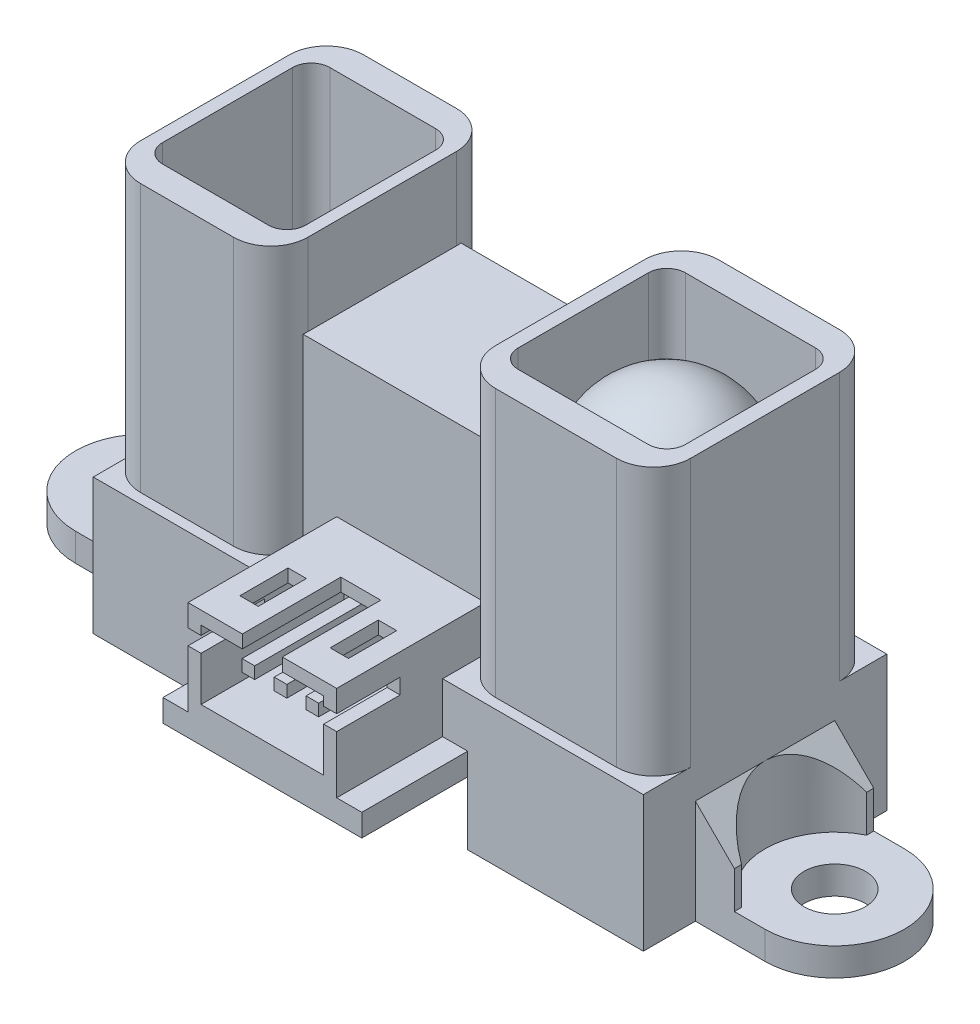
SolidWorks part; units mm, degrees
ref_plane "前视基准面" through (0, 0, 0) normal (0, 0, 1) x (1, 0, 0)
ref_plane "上视基准面" through (0, 0, 0) normal (0, 1, 0) x (1, 0, 0)
ref_plane "右视基准面" through (0, 0, 0) normal (1, 0, 0) x (0, 0, -1)
sketch "草图1" plane through (0, 0, 0) normal (0, 1, 0) x (1, 0, 0)
  line L0 (-14.8, 6.55) -> (14.8, -6.55) construction
  line L1 (-14.8, 6.55) -> (14.8, 6.55)
  line L2 (-14.8, 6.55) -> (-14.8, -6.55)
  line L3 (-14.8, -6.55) -> (14.8, -6.55)
  line L4 (14.8, 6.55) -> (14.8, -6.55)
  line L5 (14.8, 6.55) -> (-14.8, -6.55) construction
  dimension "D1" = 29.6
  dimension "D2" = 13.1
extrude "凸台-拉伸1" add sketch "草图1" along normal blind 7.3
sketch "草图2" plane through (0, 7.3, 0) normal (0, 1, 0) x (1, 0, 0)
  line L0 (14.8, -6.55) -> (14.8, 6.55) construction
  line L1 (4.3, 6) -> (14.8, 6)
  line L2 (4.3, 6) -> (4.3, -6)
  line L3 (4.3, -6) -> (14.8, -6)
  line L4 (14.8, 6) -> (14.8, -6)
  line L5 (-20.4467, 0) -> (27.7818, 0) construction
  line L6 (14.8, 6.55) -> (-14.8, 6.55) construction
  line L7 (-14.8, -6.55) -> (14.8, -6.55) construction
  line L8 (4.3, 6) -> (-21.835, 6) construction
  line L9 (4.3, -6) -> (-21.835, -6) construction
  line L10 (-14.8, 6.55) -> (-14.8, -6.55) construction
  line L11 (-14.8, 6) -> (-5.8, 6)
  line L12 (-14.8, 6) -> (-14.8, -6)
  line L13 (-14.8, -6) -> (-5.8, -6)
  line L14 (-5.8, 6) -> (-5.8, -6)
  dimension "D1" = 10.5
  dimension "D2" = 12
  dimension "D3" = 9
extrude "凸台-拉伸2" add sketch "草图2" along normal blind 14.4
sketch "草图3" plane through (0, 7.3, 0) normal (0, 1, 0) x (1, 0, 0)
  line L0 (-5.8, -6) -> (-5.8, 6) construction
  line L1 (-5.8, 4.25) -> (4.3, 4.25)
  line L2 (-5.8, 4.25) -> (-5.8, -4.25)
  line L3 (-5.8, -4.25) -> (4.3, -4.25)
  line L4 (4.3, 4.25) -> (4.3, -4.25)
  line L5 (4.3, 6) -> (4.3, -6) construction
  line L6 (-18.5434, 0) -> (19.3503, 0) construction
  dimension "D1" = 8.5
extrude "凸台-拉伸3" add sketch "草图3" along normal blind 10
fillet "圆角1" radius 2 8 edges at (14.8, 14.5, 6) (4.3, 14.5, 6) (14.8, 14.5, -6) (4.3, 14.5, -6) (-5.8, 14.5, -6) (-14.8, 14.5, -6) (-5.8, 14.5, 6) (-14.8, 14.5, 6)
sketch "草图4" plane through (0, 21.7, 0) normal (0, 1, 0) x (1, 0, 0)
  line L0 (-19.2678, 0) -> (22.6472, 0) construction
  line L2 (5.0163, -4.5) -> (14.0163, -4.5)
  line L3 (5.0163, -4.5) -> (5.0163, 4.5)
  line L4 (5.0163, 4.5) -> (14.0163, 4.5)
  line L5 (14.0163, -4.5) -> (14.0163, 4.5)
  line L6 (5.0163, -4.5) -> (14.0163, 4.5) construction
  line L7 (5.0163, 4.5) -> (14.0163, -4.5) construction
  line L8 (-14.1217, -4.5) -> (-6.4217, -4.5)
  line L9 (-14.1217, -4.5) -> (-14.1217, 4.5)
  line L10 (-14.1217, 4.5) -> (-6.4217, 4.5)
  line L11 (-6.4217, -4.5) -> (-6.4217, 4.5)
  line L12 (-14.1217, -4.5) -> (-6.4217, 4.5) construction
  line L13 (-14.1217, 4.5) -> (-6.4217, -4.5) construction
  point P3 (9.5163, 0)
  point P8 (-10.2717, 0)
  dimension "D1" = 9
  dimension "D2" = 9
  dimension "D3" = 9
  dimension "D4" = 7.7
extrude "切除-拉伸2" cut sketch "草图4" against normal blind 10
sketch "草图5" plane through (0, 0, 0) normal (0, -1, 0) x (1, 0, 0)
  line L0 (-22.468, 0) -> (25.1594, 0) construction
  line L1 (-18.55, 0) -> (18.55, 0) construction
  line L2 (-18.55, 3.75) -> (18.55, 3.75)
  line L3 (-18.55, -3.75) -> (18.55, -3.75)
  line L4 (0, 10.6195) -> (0, -15.0191) construction
  line L5 (-14.8, -6.55) -> (-14.8, 6.55) construction
  line L6 (14.8, 6.55) -> (14.8, -6.55) construction
  arc A0 (-18.55, 3.75) -> (-18.55, -3.75) centre (-18.55, 0) ccw
  arc A1 (18.55, -3.75) -> (18.55, 3.75) centre (18.55, 0) ccw
  circle A2 centre (-18.55, 0) radius 3.75 construction
  circle A3 centre (18.55, 0) radius 3.75 construction
  point P5 (0, 0)
  dimension "D2" = 7.5
extrude "凸台-拉伸4" add sketch "草图5" against normal blind 5.6
sketch "草图6" plane through (0, 0, -3.75) normal (0, 0, -1) x (-1, 0, 0)
  line L0 (0, 22.8299) -> (0, -7.404) construction
  line L1 (-14.8, 5.6) -> (-16.9, 3.5)
  line L2 (-16.9, 3.5) -> (-16.9, 1.5)
  line L3 (-16.9, 1.5) -> (-22.3, 1.5)
  line L4 (-22.3, 5.6) -> (-22.3, 0) construction
  line L5 (-22.3, 1.5) -> (-22.3, 5.6)
  line L6 (-22.3, 5.6) -> (-14.8, 5.6)
  line L7 (-22.3, 0) -> (-18.55, 0) construction
  line L8 (-14.8, 0) -> (-18.55, 0) construction
  line L9 (22.3, 1.5) -> (22.3, 5.6)
  line L10 (16.9, 1.5) -> (22.3, 1.5)
  line L11 (16.9, 3.5) -> (16.9, 1.5)
  line L12 (14.8, 5.6) -> (16.9, 3.5)
  line L13 (22.3, 5.6) -> (14.8, 5.6)
  dimension "D1" = 1.5
  dimension "D2" = 5.4
  dimension "D3" = 3.5
extrude "切除-拉伸3" cut sketch "草图6" against normal blind 12.6
sketch "草图8" plane through (0, 1.5, 0) normal (0, 1, 0) x (1, 0, 0)
  line L0 (0, 15.0449) -> (0, -16.0516) construction
  circle A0 centre (-18.55, 0) radius 3.75
  arc A1 (-18.55, 3.75) -> (-18.55, -3.75) centre (-18.55, 0) ccw construction
  circle A2 centre (18.55, 0) radius 3.75
extrude "切除-拉伸4" cut sketch "草图8" along normal blind 7.6
sketch "草图9" plane through (0, 1.5, 0) normal (0, 1, 0) x (1, 0, 0)
  line L0 (0, 13.5076) -> (0, -13.6711) construction
  circle A0 centre (-18.55, 0) radius 1.65
  arc A1 (-18.55, 3.75) -> (-18.55, -3.75) centre (-18.55, 0) ccw construction
  circle A2 centre (18.55, 0) radius 1.65
  dimension "D1" = 3.3
extrude "切除-拉伸5" cut sketch "草图9" against normal blind 7.6
sketch "草图10" plane through (0, 0, 0) normal (0, -1, 0) x (1, 0, 0)
  line L0 (14.8, -6.55) -> (-14.8, -6.55) construction
  line L1 (-14, 5.75) -> (-5.35, 5.75)
  line L2 (-14, 5.75) -> (-14, -5.75)
  line L3 (-14, -5.75) -> (14, -5.75)
  line L4 (14, 5.75) -> (14, -5.75)
  line L5 (-14.8, 6.55) -> (14.8, 6.55) construction
  line L6 (14.8, 6.55) -> (14.8, 3.75) construction
  line L7 (-14.8, 3.75) -> (-14.8, 6.55) construction
  line L8 (0, 11.9796) -> (0, -13.9627) construction
  line L9 (5.35, 5.75) -> (14, 5.75)
  line L10 (-5.35, 6.55) -> (5.35, 6.55)
  line L11 (-5.35, 6.55) -> (-5.35, 5.75)
  line L13 (5.35, 6.55) -> (5.35, 5.75)
  dimension "D1" = 0.8
  dimension "D2" = 0.8
  dimension "D3" = 0.8
  dimension "D4" = 0.8
  dimension "D5" = 10.7
extrude "切除-拉伸6" cut sketch "草图10" against normal blind 3.4
sketch "草图11" plane through (0, 0, 6.55) normal (0, 0, 1) x (1, 0, 0)
  line L1 (-5.35, 3.4) -> (5.35, 3.4)
  line L2 (-5.35, 3.4) -> (-5.35, 4.6)
  line L3 (-5.35, 4.6) -> (5.35, 4.6)
  line L4 (5.35, 3.4) -> (5.35, 4.6)
  dimension "D1" = 1.2
extrude "凸台-拉伸5" add sketch "草图11" along normal blind 5.7
sketch "草图12" plane through (0, 0, 12.25) normal (0, 0, 1) x (1, 0, 0)
  line L0 (0, -1.4842) -> (0, 11.7495) construction
  line L1 (5.35, 4.6) -> (-5.35, 4.6) construction
  line L2 (-4, 9.7) -> (4, 9.7)
  line L3 (-4, 9.7) -> (-4, 4.6)
  line L4 (-4, 4.6) -> (4, 4.6)
  line L5 (4, 9.7) -> (4, 4.6)
  line L6 (-4, 9.7) -> (4, 4.6) construction
  line L7 (-4, 4.6) -> (4, 9.7) construction
  line L8 (-14, 3.4) -> (14, 3.4) construction
  point P3 (0, 7.15)
  dimension "D1" = 8
  dimension "D2" = 6.3
extrude "凸台-拉伸6" add sketch "草图12" against normal up to surface (8 mm away) up to face at (-0.75, 12.3, 4.25)
sketch "草图13" plane through (0, 0, 12.25) normal (0, 0, 1) x (1, 0, 0)
  line L0 (0, 21.4766) -> (0, -5.0339) construction
  line L1 (4, 9.7) -> (-4, 9.7) construction
  line L2 (-3.3, 5.3) -> (3.3, 5.3)
  line L3 (-3.3, 5.3) -> (-3.3, 9)
  line L4 (-3.3, 9) -> (3.3, 9)
  line L5 (3.3, 5.3) -> (3.3, 9)
  line L6 (-3.3, 5.3) -> (3.3, 9) construction
  line L7 (-3.3, 9) -> (3.3, 5.3) construction
  line L8 (4, 4.6) -> (4, 9.7) construction
  line L9 (-4, 4.6) -> (-5.35, 4.6) construction
  point P3 (0, 7.15)
  dimension "D1" = 0.7
  dimension "D2" = 0.7
  dimension "D3" = 0.7
extrude "切除-拉伸7" cut sketch "草图13" against normal blind 7.7
sketch "草图14" plane through (-4, 0, 0) normal (-1, 0, 0) x (0, 0, 1)
  line L0 (12.25, 9.7) -> (12.25, 4.6) construction
  line L1 (12.25, 8.517) -> (8.8366, 8.517)
  line L2 (12.25, 8.517) -> (12.25, 7.6853)
  line L3 (12.25, 7.6853) -> (8.8366, 7.6853)
  line L4 (8.8366, 8.517) -> (8.8366, 7.6853)
extrude "切除-拉伸8" cut sketch "草图14" against normal blind 9.7
sketch "草图15" plane through (0, 9.7, 0) normal (0, 1, 0) x (1, 0, 0)
  line L5 (0, -0.9912) -> (0, -14.9752) construction
  line L6 (-2.9225, -7.9444) -> (-1.9332, -7.9444)
  line L7 (-2.9225, -7.9444) -> (-2.9225, -10.538)
  line L8 (-2.9225, -10.538) -> (-1.9332, -10.538)
  line L9 (-1.9332, -7.9444) -> (-1.9332, -10.538)
  line L14 (-1.0747, -12.25) -> (-1.0747, -6.9538)
  line L15 (4, -12.25) -> (-4, -12.25) construction
  line L16 (-1.0747, -6.9538) -> (1.0747, -6.9538)
  line L17 (-1.0747, -12.25) -> (1.0747, -12.25)
  line L18 (1.0747, -12.25) -> (1.0747, -6.9538)
  line L19 (2.9225, -10.538) -> (1.9332, -10.538)
  line L20 (1.9332, -7.9444) -> (1.9332, -10.538)
  line L21 (2.9225, -7.9444) -> (1.9332, -7.9444)
  line L22 (2.9225, -7.9444) -> (2.9225, -10.538)
  point P13 (0, -12.25)
  point P14 (0, -6.9538)
extrude "切除-拉伸9" cut sketch "草图15" against normal blind 2.7
sketch "草图16" plane through (0, 0, 4.55) normal (0, 0, 1) x (1, 0, 0)
  line L0 (0, 20.1561) -> (0, -6.5805) construction
  line L1 (-2.0911, 7.5446) -> (-1.4132, 7.5446)
  line L2 (-0.3607, 7.5446) -> (0.3171, 7.5446)
  line L3 (-0.3607, 7.5446) -> (-0.3607, 6.9024)
  line L4 (-0.3607, 6.9024) -> (0.3171, 6.9024)
  line L5 (0.3171, 7.5446) -> (0.3171, 6.9024)
  line L6 (-2.0911, 7.5446) -> (-2.0911, 6.9024)
  line L7 (-2.0911, 6.9024) -> (-1.4132, 6.9024)
  line L8 (-1.4132, 7.5446) -> (-1.4132, 6.9024)
  line L9 (1.3518, 7.5267) -> (2.0296, 7.5267)
  line L10 (1.3518, 7.5267) -> (1.3518, 6.8846)
  line L11 (1.3518, 6.8846) -> (2.0296, 6.8846)
  line L12 (2.0296, 7.5267) -> (2.0296, 6.8846)
extrude "凸台-拉伸7" add sketch "草图16" along normal blind 6.7
sketch "草图17" plane through (0, 11.7, 0) normal (0, 1, 0) x (1, 0, 0)
  circle A0 centre (9.5234, -0.019) radius 4.45
  dimension "D1" = 8.9
extrude "凸台-拉伸8" add sketch "草图17" along normal blind 9
fillet "圆角3" radius 4.45 1 edges at (9.5234, 20.7, 4.469)
fillet "圆角4" radius 1 4 edges at (14.0163, 16.7, 4.5) (5.0163, 16.7, 4.5) (5.0163, 16.7, -4.5) (14.0163, 16.7, -4.5)
sketch "草图18" plane through (0, 11.7, 0) normal (0, 1, 0) x (1, 0, 0)
  line L1 (-14.1217, 4.5) -> (-6.4217, 4.5)
  line L2 (-14.1217, 4.5) -> (-14.1217, -4.5)
  line L3 (-14.1217, -4.5) -> (-6.4217, -4.5)
  line L4 (-6.4217, 4.5) -> (-6.4217, -4.5)
extrude "切除-拉伸10" cut sketch "草图18" against normal blind 2
sketch "草图19" plane through (0, 9.7, 0) normal (0, 1, 0) x (1, 0, 0)
  circle A0 centre (-10.28, 0.0322) radius 3.5
  dimension "D1" = 7
extrude "凸台-拉伸9" add sketch "草图19" along normal blind 7
fillet "圆角6" radius 3.5 1 edges at (-10.28, 16.7, 3.4678)
fillet "圆角7" radius 1 4 edges at (-6.4217, 15.7, 4.5) (-14.1217, 15.7, 4.5) (-14.1217, 15.7, -4.5) (-6.4217, 15.7, -4.5)
